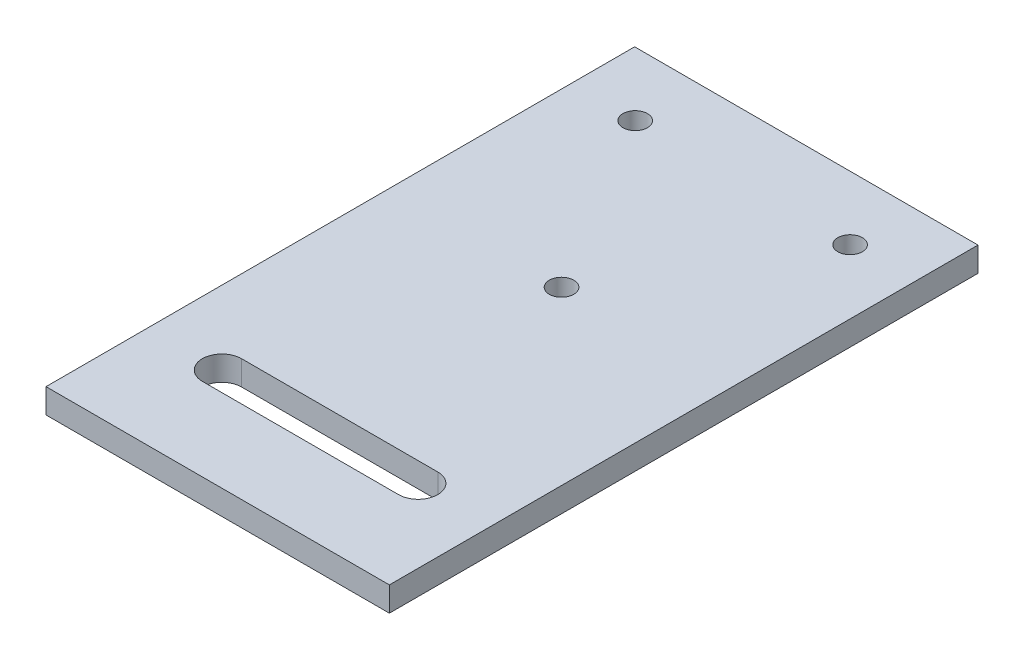
SolidWorks part; units mm, degrees
ref_plane "Front Plane" through (0, 0, 0) normal (0, 0, 1) x (1, 0, 0)
ref_plane "Top Plane" through (0, 0, 0) normal (0, 1, 0) x (1, 0, 0)
ref_plane "Right Plane" through (0, 0, 0) normal (1, 0, 0) x (0, 0, -1)
sketch "Sketch1" plane through (0, 0, 0) normal (0, 1, 0) x (1, 0, 0)
  line L0 (35, 2.946) -> (35, -117.054) construction
  line L1 (0, 2.946) -> (70, 2.946)
  line L2 (0, 2.946) -> (0, -117.054)
  line L3 (0, -117.054) -> (70, -117.054)
  line L4 (70, 2.946) -> (70, -117.054)
  line L5 (35, -117.054) -> (0, -57.054) construction
  line L6 (0, -57.054) -> (70, -57.054) construction
  line L7 (15, -96.1822) -> (55, -96.1822) construction
  line L8 (15, -92.1822) -> (55, -92.1822)
  line L9 (15, -100.1822) -> (55, -100.1822)
  circle A8 centre (13.0978, -10.0346) radius 2.5
  circle A9 centre (56.9022, -10.0346) radius 2.5
  circle A10 centre (35, -46.9573) radius 2.5
  circle A11 centre (35, -96.1822) radius 4 construction
  arc A12 (15, -92.1822) -> (15, -100.1822) centre (15, -96.1822) ccw
  arc A13 (55, -100.1822) -> (55, -92.1822) centre (55, -96.1822) ccw
  point P15 (35, -96.1822)
  dimension "D3" = 8
  dimension "D5" = 5
  dimension "D6" = 5
  dimension "D9" = 4
  dimension "D1" = 70
  dimension "D2" = 120
  dimension "D7" = 20
  dimension "D8" = 20
extrude "Boss-Extrude1" add sketch "Sketch1" along normal blind 5
